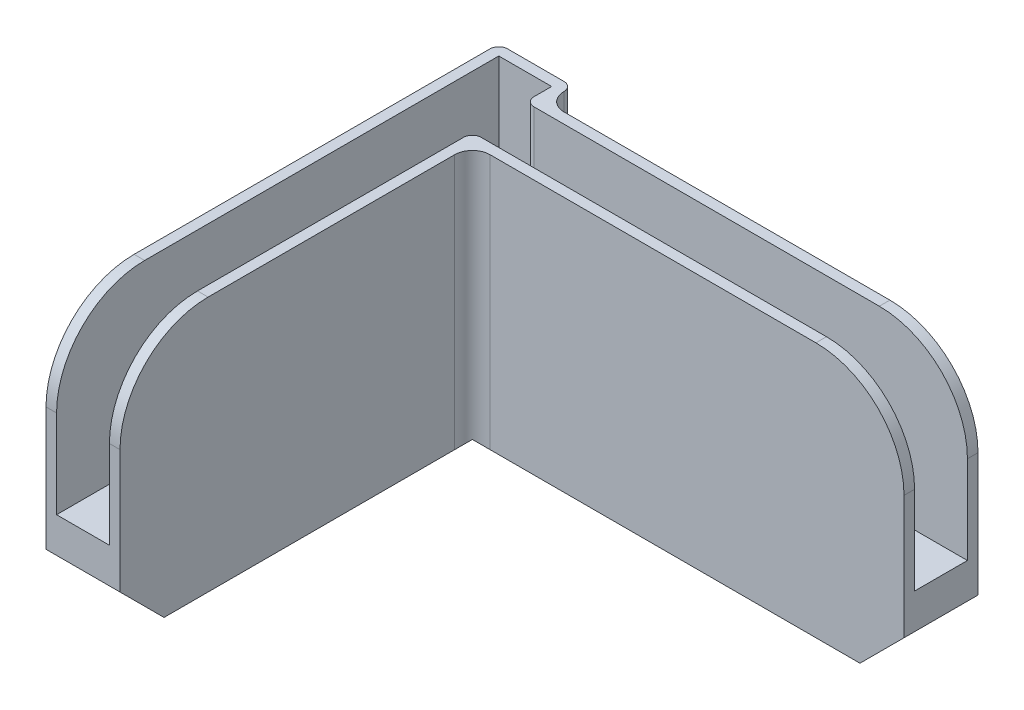
SolidWorks part; units mm, degrees
ref_plane "Front" through (0, 0, 0) normal (0, 0, 1) x (1, 0, 0)
ref_plane "Top" through (0, 0, 0) normal (0, 1, 0) x (1, 0, 0)
ref_plane "Right" through (0, 0, 0) normal (1, 0, 0) x (0, 0, -1)
sketch "Эскиз1" plane through (0, 0, 0) normal (0, 1, 0) x (1, 0, 0)
  line L0 (0, 0) -> (-49, 0)
  line L1 (-49, 0) -> (-49, -40)
  line L2 (-49, -40) -> (-55, -40)
  line L3 (-55, -40) -> (-55, 9)
  line L4 (-55, 9) -> (-49, 9)
  line L5 (-49, 9) -> (-49, 6)
  line L6 (-49, 6) -> (0, 6)
  line L7 (0, 6) -> (0, 0)
  dimension "D1" = 49
  dimension "D2" = 40
  dimension "D3" = 3
  dimension "D4" = 6
  dimension "D5" = 6
  dimension "D6" = 6
extrude "Вытянуть-Тонкостенный1" add sketch "Эскиз1" along normal blind 20 thin thin type one direction wall 1.2
sketch "Эскиз2" plane through (0, 0, 0) normal (0, -1, 0) x (1, 0, 0)
  line L0 (-56.2, 41.2) -> (-47.8, 41.2)
  line L1 (-47.8, 41.2) -> (-47.8, 1.2)
  line L2 (-47.8, 1.2) -> (1.2, 1.2)
  line L3 (1.2, 1.2) -> (1.2, -7.2)
  line L4 (1.2, -7.2) -> (-47.8, -7.2)
  line L5 (-47.8, -7.2) -> (-47.8, -10.2)
  line L6 (-47.8, -10.2) -> (-56.2, -10.2)
  line L7 (-56.2, -10.2) -> (-56.2, 41.2)
extrude "Бобышка-Вытянуть1" add sketch "Эскиз2" along normal blind 10
chamfer "Фаска1" distance 6 angle 45 3 edges at (-52, -10, -10.2) (1.2, -10, -3) (-52, -10, 41.2)
chamfer "Фаска2" distance 1 angle 45 3 edges at (-26.3, -10, 1.2) (-47.8, -10, 18.2) (-56.2, -10, 15.5)
sketch "Эскиз3" plane through (0, 0, 0) normal (-1, 0, 0) x (0, 0, 1)
  line L1 (0, 0) -> (-6, 0)
  line L2 (0, 0) -> (0, 20)
  line L3 (0, 20) -> (-6, 20)
  line L4 (-6, 0) -> (-6, 20)
extrude "Вырез-Вытянуть1" cut sketch "Эскиз3" against normal up to next
sketch "Эскиз4" plane through (0, 0, 40) normal (0, 0, -1) x (-1, 0, 0)
  line L1 (55, 0) -> (49, 0)
  line L2 (55, 0) -> (55, 20)
  line L3 (55, 20) -> (49, 20)
  line L4 (49, 0) -> (49, 20)
extrude "Вырез-Вытянуть2" cut sketch "Эскиз4" against normal up to next
fillet "Скругление1" radius 10 4 edges at (1.2, 20, -6.6) (1.2, 20, 0.6) (-48.4, 20, 41.2) (-55.6, 20, 41.2)
fillet "Скругление2" radius 2 2 edges at (-47.8, 5.5, 1.2) (-47.8, 6.5, -7.2)
fillet "Скругление3" radius 1 4 edges at (-56.2, 8, -10.2) (-47.8, 8, -10.2) (-49, 10, -6) (-49, 10, 0)
